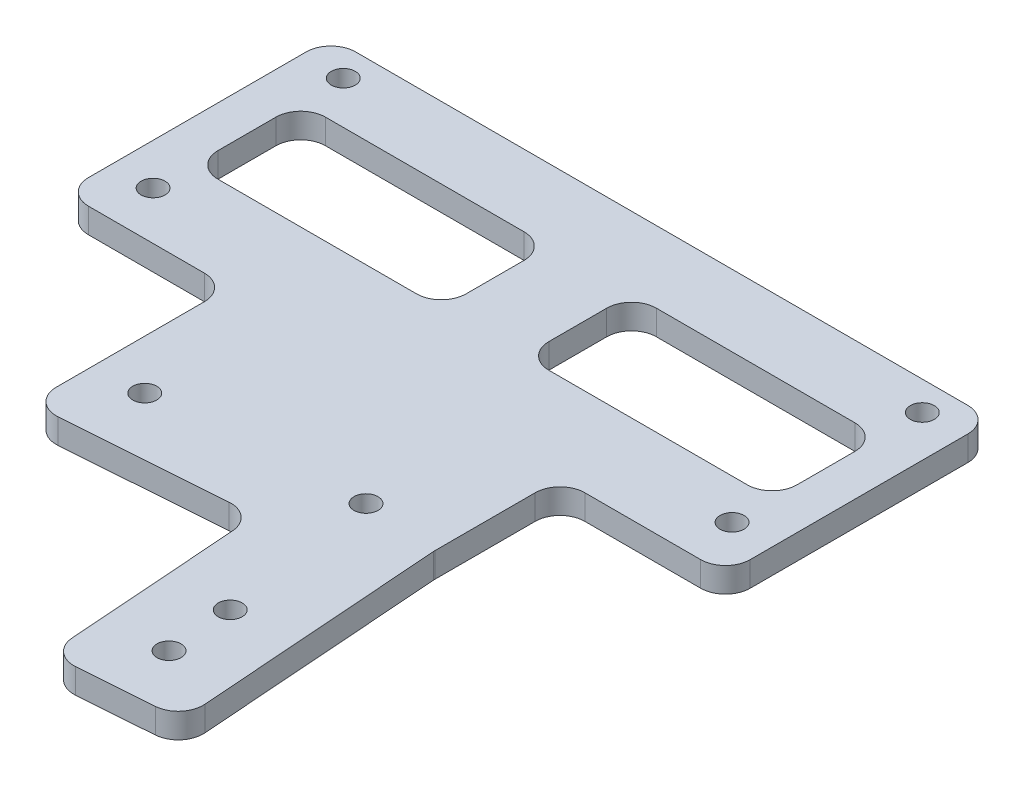
SolidWorks part; units mm, degrees
material "Thornel Mat VMA"
ref_plane "前视基准面" through (0, 0, 0) normal (0, 0, 1) x (1, 0, 0)
ref_plane "上视基准面" through (0, 0, 0) normal (0, 1, 0) x (1, 0, 0)
ref_plane "右视基准面" through (0, 0, 0) normal (1, 0, 0) x (0, 0, -1)
other "Configuration Table"
sketch "草图1" plane through (0, 0, 0) normal (0, 1, 0) x (1, 0, 0)
  line L0 (0, 44.5579) -> (0, -29.9684) construction
  line L1 (-20, -7.6) -> (20, -7.6) construction
  line L2 (-20, -7.6) -> (-20, 7.6)
  line L3 (-20, 7.6) -> (20, 7.6) construction
  line L4 (20, -7.6) -> (20, 7.6)
  line L5 (-20, -7.6) -> (20, 7.6) construction
  line L6 (-20, 7.6) -> (20, -7.6) construction
  line L7 (-40, 7.6) -> (40, 7.6) construction
  line L8 (-40, 7.6) -> (-40, 41.9)
  line L9 (-40, 41.9) -> (40, 41.9)
  line L10 (40, 7.6) -> (40, 41.9)
  line L11 (-40, 7.6) -> (-20, 7.6)
  line L12 (20, 7.6) -> (40, 7.6)
  line L13 (-44.2356, 13.4) -> (49.9292, 13.4) construction
  line L14 (-48.6365, 36.4) -> (50.9677, 36.4) construction
  line L15 (-35, 13.4) -> (-35, 36.4) construction
  line L16 (-17.4602, -8.8249) -> (13.7779, -6.5505) construction
  line L17 (-51.6355, 24.75) -> (49.9036, 24.75) construction
  line L18 (35, 36.4) -> (35, 13.4) construction
  line L19 (-35, 18.25) -> (-5, 18.25)
  line L20 (-35, 18.25) -> (-35, 31.25)
  line L21 (-35, 31.25) -> (-5, 31.25)
  line L22 (-5, 18.25) -> (-5, 31.25)
  line L23 (5, 18.25) -> (5, 31.25)
  line L24 (35, 18.25) -> (5, 18.25)
  line L25 (35, 18.25) -> (35, 31.25)
  line L26 (35, 31.25) -> (5, 31.25)
  line L27 (-311.6829, 179.6676) -> (-312.7721, 164.7072) construction
  line L28 (-311.6829, 189.6676) -> (368.3171, 189.6676) construction
  line L29 (-311.6829, 189.6676) -> (-311.6829, 204.6676) construction
  line L30 (-311.6829, 204.6676) -> (368.3171, 204.6676) construction
  line L31 (368.3171, 189.6676) -> (368.3171, 204.6676) construction
  line L32 (-311.6829, 179.6676) -> (368.3171, 130.1576) construction
  line L33 (-312.7721, 164.7072) -> (367.2279, 115.1972) construction
  line L34 (368.3171, 130.1576) -> (367.2279, 115.1972) construction
  line L35 (-311.6829, 189.6676) -> (-311.6829, 179.6676) construction
  line L36 (-311.6829, 179.6676) -> (-291.7357, 178.2153) construction
  line L37 (-291.7357, 178.2153) -> (-290.9018, 189.6676) construction
  line L38 (-290.9018, 189.6676) -> (-311.6829, 189.6676) construction
  line L39 (342.5706, 189.6676) -> (338.3963, 132.3361) construction
  line L40 (338.3963, 132.3361) -> (368.3171, 130.1576) construction
  line L41 (368.3171, 130.1576) -> (368.3171, 189.6676) construction
  line L42 (368.3171, 189.6676) -> (342.5706, 189.6676) construction
  line L43 (258.6075, 138.1454) -> (259.9416, 156.4681) construction
  line L44 (258.6075, 138.1454) -> (-357.3954, 138.1454) construction
  line L45 (-311.6829, 189.6676) -> (-290.9018, 189.6676) construction
  line L46 (-311.6829, 179.6676) -> (-291.7357, 178.2153) construction
  line L47 (-20, -7.6) -> (-20, -16.5296)
  line L48 (-20, -16.5296) -> (20.4358, -13.5856) construction
  line L49 (20.4358, -13.5856) -> (20, -7.6)
  line L50 (312.7721, 164.7072) -> (-367.2279, 115.1972) construction
  line L51 (12.2249, -4.094) -> (15.097, -43.5419) construction
  line L52 (20.4358, -13.5856) -> (22.3964, -40.5143)
  line L53 (22.3964, -40.5143) -> (7.4361, -41.6035)
  line L54 (7.4361, -41.6035) -> (5.4754, -14.6748)
  line L55 (5.4754, -14.6748) -> (-20, -16.5296)
  circle A0 centre (-35, 13.4) radius 1.45
  circle A1 centre (-35, 36.4) radius 1.45
  circle A2 centre (35, 13.4) radius 1.45
  circle A3 centre (35, 36.4) radius 1.45
  circle A4 centre (-14.0294, -8.5751) radius 1.45
  circle A6 centre (10.9046, -6.7597) radius 1.45
  circle A7 centre (13.827, -26.0985) radius 1.45
  circle A8 centre (14.4079, -34.0774) radius 1.45
  point P0 (0, 0)
  point P32 (0, 24.75)
  point P69 (22.2061, -37.9003)
  dimension "D7" = 2.9
  dimension "D8" = 35
  dimension "D9" = 25
  dimension "D5" = 5.8
  dimension "D20" = 19.5
  dimension "D21" = 8
  dimension "D23" = 2.9
  dimension "D25" = 7
  dimension "D1" = 15.2
  dimension "D2" = 40
  dimension "D3" = 80
  dimension "D4" = 23
  dimension "D6" = 5.5
  dimension "D10" = 30
  dimension "D11" = 13
  dimension "D12" = 7.5
  dimension "D13" = 35
  dimension "D14" = 15
  dimension "D15" = 15
  dimension "D16" = 680
  dimension "D17" = 20
  dimension "D18" = 80
  dimension "D19" = 681.8
  dimension "D22" = 7.5
  dimension "D24" = 7.5
extrude "凸台-拉伸1" add sketch "草图1" along normal blind 3
sketch "草图2" plane through (0, 3, 0) normal (0, 1, 0) x (1, 0, 0)
  line L0 (40, 7.6) -> (40, 41.9) construction
  line L1 (-40, 41.9) -> (40, 41.9)
  line L2 (-40, 41.9) -> (-40, 39.9)
  line L3 (-40, 39.9) -> (40, 39.9)
  line L4 (40, 41.9) -> (40, 39.9)
  dimension "D1" = 2
extrude "切除-拉伸1" cut sketch "草图2" against normal through all
fillet "圆角1" radius 3 19 edges at (-35, 1.5, -31.25) (-35, 1.5, -18.25) (-5, 1.5, -18.25) (-5, 1.5, -31.25) (-20, 1.5, -7.6) (-40, 1.5, -7.6) (40, 1.5, -7.6) (20, 1.5, -7.6) (40, 1.5, -39.9) (-40, 1.5, -39.9) (35, 1.5, -31.25) (5, 1.5, -18.25) (35, 1.5, -18.25) (5, 1.5, -31.25) (20, 1.5, 7.6) (22.3964, 1.5, 40.5143) (-20, 1.5, 16.5296) (7.4361, 1.5, 41.6035) (5.4754, 1.5, 14.6748)
